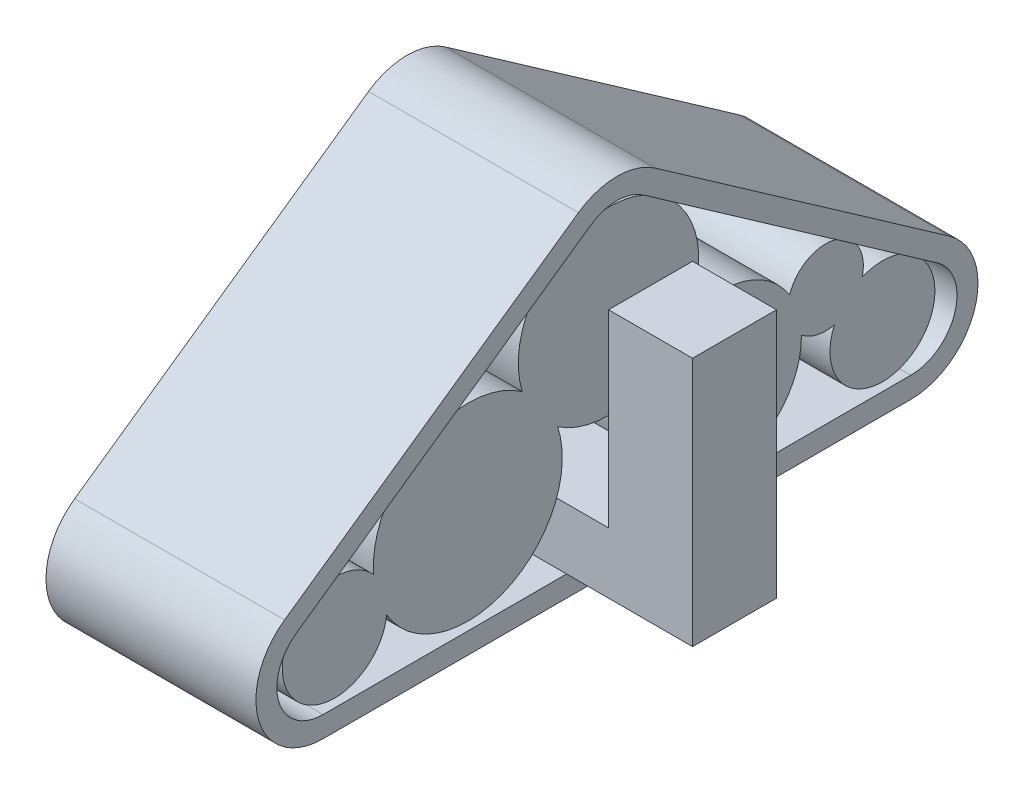
SolidWorks part; units mm, degrees
material "Polyethylene Cross-Linked"
ref_plane "Front" through (0, 0, 0) normal (0, 0, 1) x (1, 0, 0)
ref_plane "Top" through (0, 0, 0) normal (0, 1, 0) x (1, 0, 0)
ref_plane "Right" through (0, 0, 0) normal (1, 0, 0) x (0, 0, -1)
sketch "Sketch1" plane through (0, 0, 0) normal (1, 0, 0) x (0, 0, -1)
  line L0 (3, 0) -> (-3, 0)
  line L1 (6.641, 0) -> (-6.641, 0) construction
  line L2 (-3, 0) -> (-3.5, 0)
  line L3 (-3.9589, 1.4553) -> (-0.4589, 3.906)
  line L4 (0, 2.325) -> (0, -2.325) construction
  line L5 (3.9589, 1.4553) -> (0.4589, 3.906)
  line L6 (3, 0) -> (3.5, 0)
  line L8 (0.3155, 3.7013) -> (3.8155, 1.2505)
  line L9 (3.5, 0.25) -> (-3.5, 0.25)
  line L10 (-0.3155, 3.7013) -> (-3.8155, 1.2505)
  line L11 (0, 3.8797) -> (0, 3.2507)
  arc A0 (3.9589, 1.4553) -> (3.5, 0) centre (3.5, 0.8) cw
  arc A1 (-3.5, 0) -> (-3.9589, 1.4553) centre (-3.5, 0.8) cw
  arc A2 (-0.4589, 3.906) -> (0.4589, 3.906) centre (0, 3.2507) cw
  arc A3 (-3.8155, 1.2505) -> (-3.5, 0.25) centre (-3.5, 0.8) ccw
  arc A5 (3.8155, 1.2505) -> (3.5, 0.25) centre (3.5, 0.8) cw
  arc A6 (0.3155, 3.7013) -> (-0.3155, 3.7013) centre (0, 3.2507) ccw
  point P11 (0, 0)
  point P13 (6.0373, 0)
  point P16 (-6.0373, 0)
  point P19 (0, 4.2273)
  dimension "D2" = 0.8
  dimension "D4" = 0.8
  dimension "D5" = 1.1
  dimension "D6" = 1.1
  dimension "D1" = 7
  dimension "D3" = 35
  dimension "D7" = 0.25
extrude "Treads" add sketch "Sketch1" along normal blind 2.5 contours L8 A6 L10 A3 L9 A5 | L10 A3 L9 A5 L8 A6 | L3 A2 L5 A0 L6 L0 L2 A1 region at (0, 1.5312, 0)
ref_plane "Plane1" through (1.25, 0, 0) normal (1, 0, 0) x (0, 0, -1)
sketch "Sketch3" plane through (1.25, 0, 0) normal (1, 0, 0) x (0, 0, -1)
  line L0 (-0.3155, 3.7013) -> (-3.8155, 1.2505) construction
  line L1 (3.5, 0.25) -> (-3.5, 0.25) construction
  line L2 (0, 1.375) -> (0, -1.375) construction
  line L7 (-0.6, 0.25) -> (0.4, 0.25)
  line L8 (-0.6, 0.25) -> (-0.6, 0.975)
  line L9 (0.4, 0.25) -> (0.4, 0.975)
  line L10 (0.4, 0.975) -> (-0.6, 0.975)
  line L11 (0.3155, 3.7013) -> (3.8155, 1.2505) construction
  circle A0 centre (-3.2621, 0.875) radius 0.625
  circle A1 centre (3.2621, 0.875) radius 0.625
  circle A2 centre (-1.6763, 1.375) radius 1.125
  circle A3 centre (0, 2.6098) radius 1.075
  circle A4 centre (1.3472, 1.2) radius 0.95
  circle A5 centre (2.5852, 1.5627) radius 0.45
  point P6 (0, 0.5)
  dimension "D1" = 1.25
  dimension "D2" = 0.625
  dimension "D3" = 0.625
  dimension "D6" = 2.25
  dimension "D7" = 1.125
  dimension "D8" = 1.125
  dimension "D9" = 2.15
  dimension "D10" = 1.075
  dimension "D11" = 1.9
  dimension "D12" = 0.95
  dimension "D13" = 1.95
  dimension "D15" = 0.9
  dimension "D16" = 0.45
  dimension "D4" = 1
  dimension "D5" = 0.725
  dimension "D14" = 0.6
  dimension "D17" = 1.29
extrude "Circles" add sketch "Sketch3" along normal blind 1.15 and the other way blind 1.15 separate body contours A2 A0 | A3 A2 A0 | A4 A3 A2 | A5 A4 A3 | A4 A5 A1 | A4 A5 | A5 A1 | A1 A5 | A0 | A2 | A3 region at (1.25, 1.3684, 1.6806) region at (1.25, 0.8706, 3.2762) region at (1.25, 2.6251, -0.0074) region at (1.25, 1.1901, -1.3418) region at (1.25, 1.5871, -2.593) region at (1.25, 1.4527, -2.2099) region at (1.25, 0.8632, -3.2738) region at (1.25, 1.2825, -2.861)
extrude "Bottom of Connector" add sketch "Sketch3<5>" along normal blind 2.75 and the other way blind 1.25 contours L9 L10 L8 L7 region at (1.25, 0.6125, 0.1)
sketch "Sketch3<5>" plane through (1.25, 0, 0) normal (1, 0, 0) x (0, 0, -1) same geometry as "Sketch3"
sketch "Sketch4" plane through (0, 0.975, 0) normal (0, 1, 0) x (1, 0, 0)
  line L0 (0, -0.6) -> (4, -0.6) construction
  line L1 (4, 0.4) -> (3, 0.4)
  line L2 (4, 0.4) -> (4, -0.6)
  line L3 (4, -0.6) -> (3, -0.6)
  line L4 (3, 0.4) -> (3, -0.6)
  dimension "D1" = 1
extrude "Top of Connector" add sketch "Sketch4" along normal blind 2.25
scale "Scale1" bodies to scale 104 102 scale about origin uniform scaling yes scale factor 1.8
